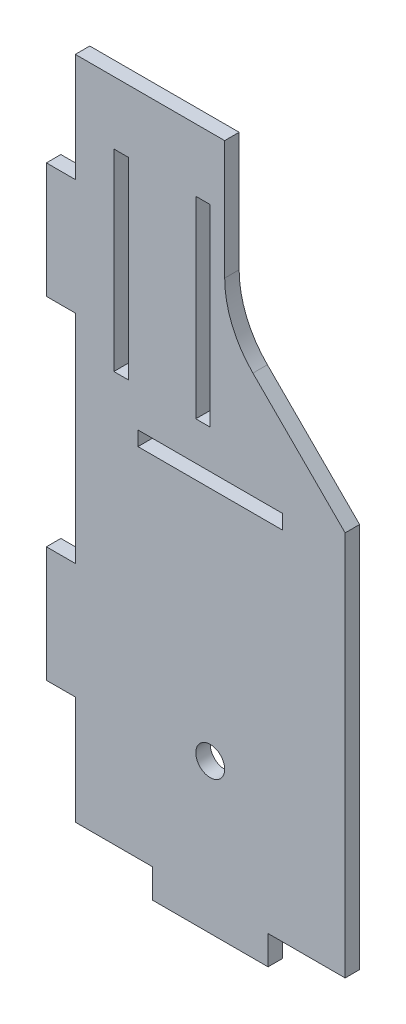
SolidWorks part; units mm, degrees
ref_plane "Front Plane" through (0, 0, 0) normal (0, 0, 1) x (1, 0, 0)
ref_plane "Top Plane" through (0, 0, 0) normal (0, 1, 0) x (1, 0, 0)
ref_plane "Right Plane" through (0, 0, 0) normal (1, 0, 0) x (0, 0, -1)
sketch "Sketch1" plane through (0, 0, 0) normal (0, 0, 1) x (1, 0, 0)
  line L0 (-56, 138) -> (-56, 0)
  line L1 (-56, 0) -> (0, 0)
  line L2 (0, 0) -> (0, 77)
  line L3 (0, 77) -> (-31, 77)
  line L4 (-31, 77) -> (-31, 138)
  line L5 (-31, 138) -> (-56, 138)
  point P6 (0, 0)
  dimension "D1" = 77
  dimension "D2" = 56
  dimension "D3" = 25
  dimension "D4" = 138
extrude "BaseShape" add sketch "Sketch1" along normal blind 3
sketch "Sketch2" plane through (0, 0, 3) normal (0, 0, 1) x (1, 0, 0)
  line L0 (-56, 138) -> (-56, 0) construction
  line L1 (-56, 0) -> (0, 0) construction
  circle A0 centre (-28, 25) radius 3
  dimension "D1" = 6
  dimension "D2" = 28
  dimension "D3" = 25
extrude "ShaftHoles" cut sketch "Sketch2" against normal through all
sketch "Sketch4" plane through (0, 0, 3) normal (0, 0, 1) x (1, 0, 0)
  line L0 (-31, 77) -> (-31, 138) construction
  line L1 (0, 77) -> (-31, 77)
  line L2 (0, 77) -> (0, 80)
  line L3 (0, 80) -> (-31, 80) construction
  line L4 (-31, 77) -> (-31, 80)
  line L5 (-56, 138) -> (-56, 0) construction
  line L6 (-56, 115.5) -> (-62, 115.5)
  line L7 (-56, 115.5) -> (-56, 91.5)
  line L8 (-56, 91.5) -> (-62, 91.5)
  line L9 (-62, 115.5) -> (-62, 91.5)
  line L10 (-56, 0) -> (0, 0) construction
  line L11 (-56, 46.5) -> (-62, 46.5)
  line L12 (-56, 46.5) -> (-56, 22.5)
  line L13 (-56, 22.5) -> (-62, 22.5)
  line L14 (-62, 46.5) -> (-62, 22.5)
  line L15 (-40, 0) -> (-16, 0)
  line L16 (-40, 0) -> (-40, -6)
  line L17 (-40, -6) -> (-16, -6)
  line L18 (-16, 0) -> (-16, -6)
  line L19 (-56, 115.5) -> (-56, 138) construction
  line L20 (-56, 22.5) -> (-56, 0) construction
  line L21 (-56, 69) -> (-56, 91.5) construction
  line L22 (-56, 46.5) -> (-56, 69) construction
  line L23 (-56, 0) -> (-56, 69) construction
  line L24 (-40, 0) -> (-56, 0) construction
  line L25 (-16, 0) -> (0, 0) construction
  line L26 (-25, 80) -> (0, 80)
  line L27 (-31, 138) -> (-25, 138)
  line L28 (-31, 138) -> (-31, 80)
  line L29 (-31, 80) -> (-25, 80) construction
  line L30 (-25, 138) -> (-25, 80)
  point P23 (-56, 69)
  point P28 (-56, 34.5)
  point P32 (-56, 34.5)
  dimension "D1" = 3
  dimension "D2" = 6
  dimension "D3" = 24
  dimension "D4" = 6
extrude "Fingers" add sketch "Sketch4" against normal up to surface (3 mm away) up to face at (-25, 25, 0)
sketch "Sketch5" plane through (0, 0, 3) normal (0, 0, 1) x (1, 0, 0)
  line L1 (-43, 77) -> (-13, 77)
  line L2 (-43, 77) -> (-43, 74)
  line L3 (-43, 74) -> (-13, 74)
  line L4 (-13, 77) -> (-13, 74)
  line L5 (-56, 91.5) -> (-56, 46.5) construction
  line L6 (-56, 138) -> (-56, 115.5) construction
  line L7 (-48, 125) -> (-45, 125)
  line L8 (-48, 125) -> (-48, 85)
  line L9 (-48, 85) -> (-45, 85)
  line L10 (-45, 125) -> (-45, 85)
  line L11 (0, 80) -> (-25, 80) construction
  line L12 (-25, 80) -> (-25, 138) construction
  line L13 (-31, 125) -> (-28, 125)
  line L14 (-31, 125) -> (-31, 85)
  line L15 (-31, 85) -> (-28, 85)
  line L16 (-28, 125) -> (-28, 85)
  point P20 (-29.5, 85)
  dimension "D1" = 3
  dimension "D2" = 3
  dimension "D3" = 30
  dimension "D4" = 13
  dimension "D5" = 8
  dimension "D6" = 3
  dimension "D7" = 3
  dimension "D8" = 3
  dimension "D9" = 40
  dimension "D10" = 8
extrude "Grooves" cut sketch "Sketch5" against normal through all
chamfer "Chamfer1" distance 25 angle 45 1 edges at (-25, 80, 1.5)
fillet "Fillet2" radius 20 1 edges at (-25, 105, 1.5)
